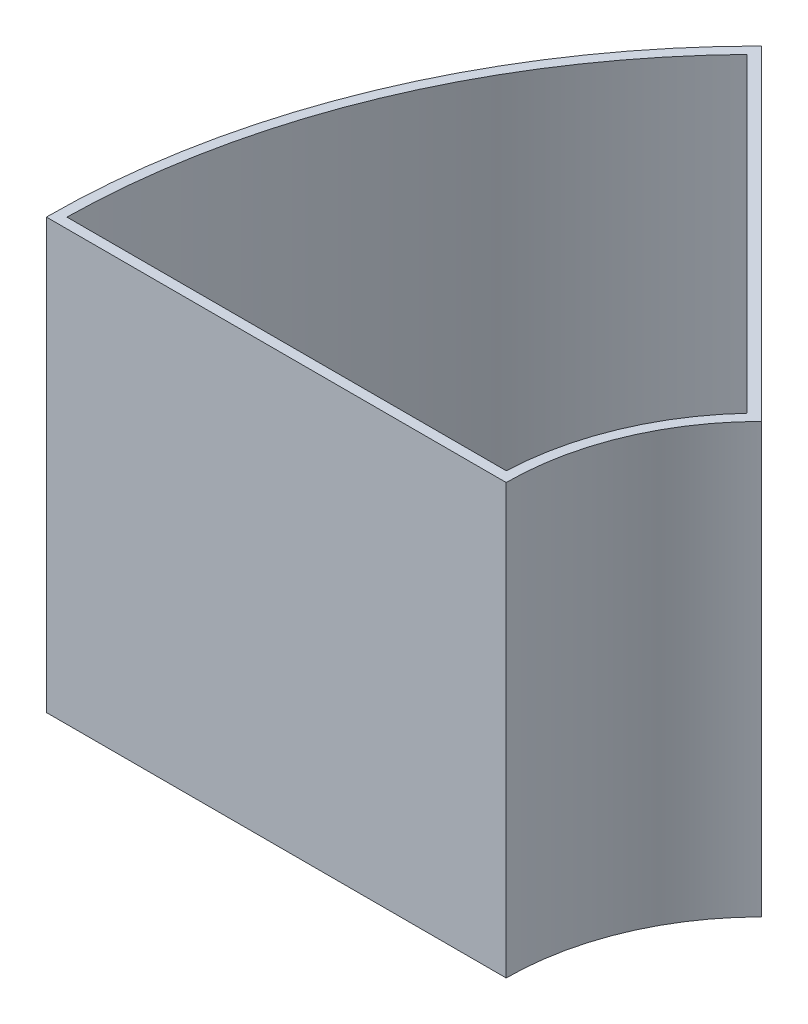
SolidWorks part; units mm, degrees
ref_plane "Alzado" through (0, 0, 0) normal (0, 0, 1) x (1, 0, 0)
ref_plane "Planta" through (0, 0, 0) normal (0, 1, 0) x (1, 0, 0)
ref_plane "Vista lateral" through (0, 0, 0) normal (1, 0, 0) x (0, 0, -1)
sketch "Croquis1" plane through (0, 0, 0) normal (0, 1, 0) x (1, 0, 0)
  line L0 (0, 0) -> (-75, 0) construction
  line L1 (0, 0) -> (-49.4975, 49.4975) construction
  line L2 (-25, 0) -> (-70, 0)
  line L4 (-49.4975, 49.4975) -> (-17.6777, 17.6777)
  circle A0 centre (0, 0) radius 75 construction
  circle A1 centre (0, 0) radius 70 construction
  circle A2 centre (0, 0) radius 25 construction
  arc A3 (-25, 0) -> (-17.6777, 17.6777) centre (0, 0) cw
  arc A4 (-70, 0) -> (-49.4975, 49.4975) centre (0, 0) cw
  dimension "D1" = 150
  dimension "D2" = 5
  dimension "D3" = 50
  dimension "D4" = 45
extrude "Saliente-Extruir1" add sketch "Croquis1" along normal blind 40
shell "Vaciado1" thickness 1 removed face at (-42.214, 40, -17.4856)
sketch "Croquis4" plane through (0, 0, 0) normal (0, -1, 0) x (1, 0, 0)
  line L0 (-25, 0) -> (-70, 0)
  line L1 (-17.6777, -17.6777) -> (-49.4975, -49.4975)
  arc A0 (-70, 0) -> (-49.4975, -49.4975) centre (0, 0) ccw
  arc A1 (-25, 0) -> (-17.6777, -17.6777) centre (0, 0) ccw
extrude "Saliente-Extruir3" add sketch "Croquis4" along normal blind 2
sketch "Croquis2" plane through (0, -2, 0) normal (0, 1, 0) x (1, 0, 0)
  line L0 (-38.9097, 27.2449) -> (-30.7182, 21.5091)
  line L1 (-46.7784, 8.2483) -> (-36.9303, 6.5118)
  line L2 (-17.6777, 17.6777) -> (-49.4975, 49.4975) construction
  circle A0 centre (0, 0) radius 37.5 construction
  circle A1 centre (0, 0) radius 47.5 construction
  arc A2 (-36.9303, 6.5118) -> (-30.7182, 21.5091) centre (0, 0) cw
  arc A3 (-46.7784, 8.2483) -> (-38.9097, 27.2449) centre (0, 0) cw
  dimension "D1" = 75
  dimension "D2" = 95
  dimension "D3" = 10
  dimension "D4" = 25
extrude "Cortar-Extruir1" cut sketch "Croquis2" along normal blind 2
sketch "Croquis5" plane through (0, 1, 0) normal (0, 1, 0) x (1, 0, 0)
  line L0 (0, 0) -> (-64.6716, 26.7878) construction
  arc A1 (-49.4975, 49.4975) -> (-70, 0) centre (0, 0) ccw construction
  circle A2 centre (-55.4328, 22.961) radius 2.5
  dimension "D1" = 5
  dimension "D2" = 60
extrude "Cortar-Extruir2" cut sketch "Croquis5" against normal blind 2
